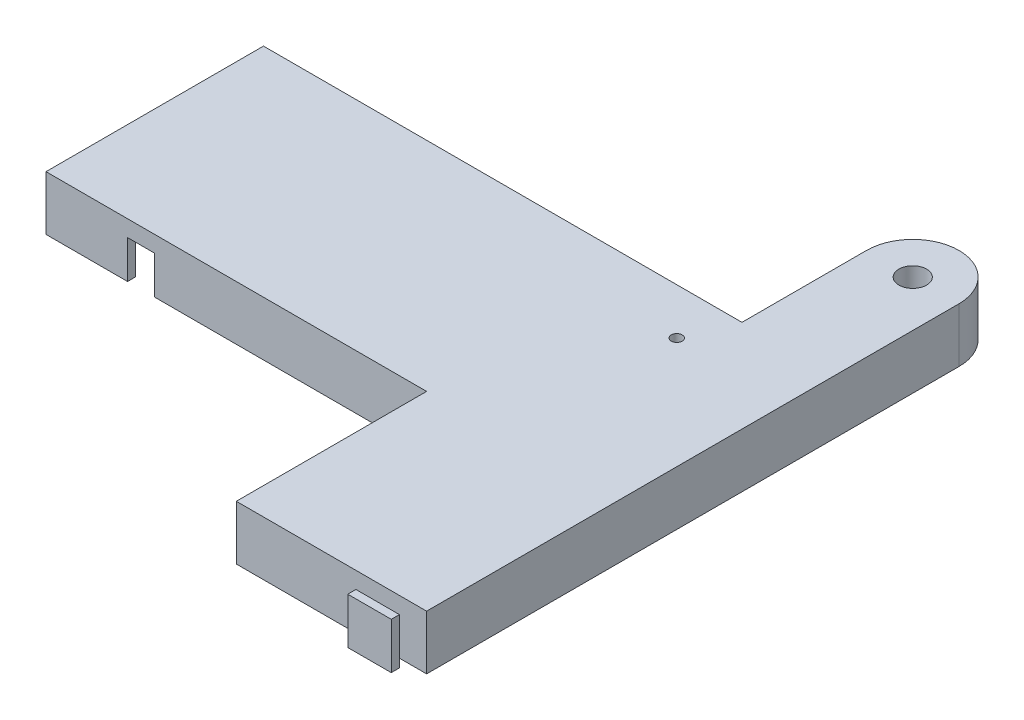
SolidWorks part; units mm, degrees
ref_plane "Front Plane" through (0, 0, 0) normal (0, 0, 1) x (1, 0, 0)
ref_plane "Top Plane" through (0, 0, 0) normal (0, 1, 0) x (1, 0, 0)
ref_plane "Right Plane" through (0, 0, 0) normal (1, 0, 0) x (0, 0, -1)
sketch "CornerSketch1" plane through (0, 0, 0) normal (0, 1, 0) x (1, 0, 0)
  line L0 (210, -70) -> (140, -70)
  line L2 (0, 80) -> (176, 80)
  line L5 (140, -70) -> (140, 0)
  line L6 (140, 0) -> (0, 0)
  line L7 (0, 80) -> (0, 0)
  line L8 (176, 125.825) -> (176, 80)
  line L10 (210, 125.825) -> (210, -70)
  arc A0 (210, 125.825) -> (176, 125.825) centre (193, 125.825) ccw
  dimension "D3" = 34
  dimension "D4" = 70
  dimension "D6" = 45.825
  dimension "D2" = 210
  dimension "D5" = 150
  dimension "D7" = 80
extrude "CornerBoss-Extrude1" add sketch "CornerSketch1" along normal blind 20
shell "Shell1" thickness 3 removed face at (131.5, 0, -36.0813)
sketch "PadSketch2" plane through (0, 17, 0) normal (0, -1, 0) x (1, 0, 0)
  line L0 (210, 70) -> (210, -125.825) construction
  line L1 (176, -80) -> (0, -80) construction
  circle A0 centre (193, -125.825) radius 12
  circle A1 centre (169, -63) radius 5
  dimension "D2" = 10
  dimension "D1" = 24
  dimension "D3" = 41
  dimension "D4" = 17
extrude "PadBoss-Extrude2" add sketch "PadSketch2" along normal blind 10
sketch "StepperRodHoleSketch3" plane through (0, 7, 0) normal (0, -1, 0) x (1, 0, 0)
  circle A0 centre (193, -125.825) radius 5.1
  circle A1 centre (169, -63) radius 2
  dimension "D1" = 10.2
  dimension "D2" = 4
extrude "StepperRodHoleCut-Extrude1" cut sketch "StepperRodHoleSketch3" against normal through all
sketch "ThreadedNutMountHolesSketch4" plane through (0, 7, 0) normal (0, -1, 0) x (-1, 0, 0)
  circle A8 centre (-193, 133.825) radius 2
  circle A9 centre (-185, 125.825) radius 2
  circle A10 centre (-201, 125.825) radius 2
  circle A11 centre (-193, 117.825) radius 2
  dimension "D1" = 4
  dimension "D3" = 16
  dimension "D4" = 8
  dimension "D5" = 16
extrude "ThreadedNutMountHolesCut-Extrude2" cut sketch "ThreadedNutMountHolesSketch4" against normal blind 10
sketch "TLPegHoleSketch1" plane through (0, 0, 0) normal (-1, 0, 0) x (0, 0, 1)
  line L1 (-70, 14) -> (-60, 14)
  line L2 (-70, 14) -> (-70, 0)
  line L3 (-70, 0) -> (-60, 0)
  line L4 (-60, 14) -> (-60, 0)
  line L7 (-80, 0) -> (0, 0) construction
  line L8 (-80, 20) -> (-80, 0) construction
  dimension "D2" = 10
  dimension "D1" = 10
  dimension "D3" = 14
extrude "TLPegHoleCut-Extrude1" cut sketch "TLPegHoleSketch1" against normal blind 3
sketch "BottomPegSketch2" plane through (0, 0, 70) normal (0, 0, 1) x (1, 0, 0)
  line L1 (190.1, 13.9) -> (199.9, 13.9)
  line L2 (190.1, 13.9) -> (190.1, 0)
  line L3 (190.1, 0) -> (199.9, 0)
  line L4 (199.9, 13.9) -> (199.9, 0)
  line L6 (210, 20) -> (210, 0) construction
  line L7 (140, 0) -> (210, 0) construction
  dimension "D2" = 13.9
  dimension "D3" = 9.8
  dimension "D1" = 10.1
extrude "BottomPegBoss-Extrude1" add sketch "BottomPegSketch2" along normal blind 3.1
sketch "BottomPegCapSketch3" plane through (0, 0, 73.1) normal (0, 0, 1) x (1, 0, 0)
  line L1 (187.1, 17) -> (203.1, 17)
  line L2 (187.1, 17) -> (187.1, 0)
  line L3 (187.1, 0) -> (203.1, 0)
  line L4 (203.1, 17) -> (203.1, 0)
  line L6 (140, 0) -> (190.1, 0) construction
  line L7 (190.1, 13.9) -> (190.1, 0) construction
  dimension "D1" = 16
  dimension "D3" = 17
  dimension "D2" = 3
extrude "BottomPegCapBoss-Extrude2" add sketch "BottomPegCapSketch3" along normal blind 3
sketch "BedCenterHoleCutSketch1" plane through (0, 0, 0) normal (0, 0, 1) x (1, 0, 0)
  line L0 (0, 0) -> (140, 0) construction
  line L1 (30, 14) -> (40, 14)
  line L2 (30, 14) -> (30, 0)
  line L3 (30, 0) -> (40, 0)
  line L4 (40, 14) -> (40, 0)
  line L5 (140, 20) -> (140, 0) construction
  dimension "D2" = 10
  dimension "D1" = 14
  dimension "D3" = 100
extrude "BedCenterHoleCut-Extrude1" cut sketch "BedCenterHoleCutSketch1" against normal blind 3
equation "\"BedThickness\"= 20mm"
equation "\"BedToBuildPlateStandoffHolesDistanceFromLeftOrRight\"= \"BuildPlateStandoffHolesDistanceFromLeftOrRight\" + \"BedIncreasedByWidth\" / 2'Equals 17"
equation "\"BedToBuildPlateStandoffHolesDistanceFromBack\"= \"BuildPlateStandoffHolesDistanceFromBack\" + \"BedIncreasedByLength\" / 2'Equals 41"
equation "\"BedLLongSide\"= \"BedThirdSize\" * 3'Equals 210"
equation "\"BedLShortSide\"= \"BedThirdSize\" * 2'Equals 140"
equation "\"BedIncreasedByWidth\"= 20mm"
equation "\"BedIncreasedByLength\"= 0mm"
equation "\"BedThirdSize\"= 70mm"
equation "\"BedOverlap\"= 20mm"
equation "\"D3@TLPegHoleSketch1\"=\"BedPegHoleHeight\""
equation "\"StandardWallThickness\"= 3mm"
equation "\"D1@CornerBoss-Extrude1\"=\"BedThickness\""
equation "\"D1@TLPegHoleCut-Extrude1\" = \"StandardWallThickness\""
equation "\"D1@BottomPegBoss-Extrude1\"=\"BedPegBoss\""
equation "\"D2@BottomPegCapSketch3\"=\"StandardWallThickness\""
equation "\"D1@BottomPegCapBoss-Extrude2\" = \"StandardWallThickness\""
equation "\"LeadScrewNutPadSize\"= \"LeadScrewNutMountingHoleFlangeDiameter\" + 2mm'Equals 24"
equation "\"BedToBuildPlateStandoffPadSize\"= 10mm"
equation "\"D1@PadSketch2\" = \"LeadScrewNutPadSize\""
equation "\"D2@PadSketch2\" = \"BedToBuildPlateStandoffPadSize\""
equation "\"D3@PadSketch2\"=\"BedToBuildPlateStandoffHolesDistanceFromBack\""
equation "\"D4@PadSketch2\"=\"BedToBuildPlateStandoffHolesDistanceFromLeftOrRight\""
equation "\"D2@StepperRodHoleSketch3\"=\"M3HeatInsertHoleDiameter\""
equation "\"BuildPlateStandoffHolesDistanceFromLeftOrRight\"= 7mm"
equation "\"BuildPlateStandoffHolesDistanceFromBack\"= 41mm"
equation "\"D1@StepperRodHoleSketch3\"=\"LeadScrewNutInnerShaftFlangeDiameter\""
equation "\"BedLWidth\"= \"BedThirdSize\"'Equals 70"
equation "\"D4@CornerSketch1\"=\"BedLWidth\" + \"BedIncreasedByLength\"/2"
equation "\"D2@CornerSketch1\"=\"BedLLongSide\""
equation "\"D7@CornerSketch1\"=\"BedLWidth\" +\"BedOverlap\"/2"
equation "\"DistanceFromBedSideToStepperHole\"= ( \"DistanceBetweenLeftToRightStepperHoles\" - \"BedWidth\" ) / 2'Equals 45.825"
equation "\"RailThickness\"= .125in'Spec"
equation "\"DistanceBetweenLeftToRightStepperHoles\"= \"FrontBackRailLength\" - \"StepperMountingHoleOffsetFromLeftOrRightSide\" * 2 - \"StepperMountingHoleDistance\"'Equals 461.65"
equation "\"BedInnerSquareWidth\"= \"BedThirdSize\" * 3'Equals 210"
equation "\"FrontBackRailLength\"= 510mm"
equation "\"StepperMountingHoleOffsetFromItsSide\"= 5.5mm'Spec"
equation "\"StepperMountingHoleOffsetFromLeftOrRightSide\"= \"StepperMountingHoleOffsetFromItsSide\" + \"RailThickness\""
equation "\"StepperMountingHoleDistance\"= 31mm'Spec"
equation "\"BedWidth\"= \"BedInnerSquareWidth\" + \"BedLWidth\" * 2 + \"BedIncreasedByWidth\"'Equals 370"
equation "\"D6@CornerSketch1\"=\"DistanceFromBedSideToStepperHole\""
equation "\"DistanceFromBedFrontToStepperHole\"= \"LeadScrewNutPadSize\" + 10mm"
equation "\"D3@CornerSketch1\"=\"DistanceFromBedFrontToStepperHole\""
equation "\"D5@CornerSketch1\"=\"BedLShortSide\" +\"BedIncreasedByWidth\"/2"
equation "\"LeadScrewNutInnerShaftFlangeDiameter\"= 10.2mm'Spec"
equation "\"LeadScrewNutMountHoleDiameter\" = \"M3HeatInsertHoleDiameter\"'Spec is 4.1 but smaller for tapping"
equation "\"LeadScrewNutMountingHoleFlangeDiameter\"= 22mm'Spec"
equation "\"LeadScrewNutMountingHoleDistance\"= 16mm'Spec"
equation "\"D3@ThreadedNutMountHolesSketch4\"=\"LeadScrewNutMountingHoleDistance\""
equation "\"D4@ThreadedNutMountHolesSketch4\"=\"LeadScrewNutMountingHoleDistance\"/2"
equation "\"D5@ThreadedNutMountHolesSketch4\"=\"LeadScrewNutMountingHoleDistance\""
equation "\"D2@ThreadedNutMountHolesSketch4\"=\"LeadScrewNutMountingHoleDistance\"/2"
equation "\"D1@ThreadedNutMountHolesSketch4\"=\"LeadScrewNutMountHoleDiameter\""
equation "\"LeadScrewNutPadDepth\"= \"BedThickness\" / 2'Equals 10"
equation "\"D1@ThreadedNutMountHolesCut-Extrude2\"=\"LeadScrewNutPadDepth\""
equation "\"D1@PadBoss-Extrude2\"= \"LeadScrewNutPadDepth\""
equation "\"BedPegHoleWidth\"= 10mm"
equation "\"BedPegHoleHeight\"= \"BedThickness\" - \"StandardWallThickness\" * 2'Equals 14"
equation "\"BedPegWidth\"= \"BedPegHoleWidth\" - .1mm * 2'For easier assembly"
equation "\"BedPegHeight\"= \"BedPegHoleHeight\" - .1mm'For easier assembly"
equation "\"BedTopPegOffsetFromSide\"= 10mm"
equation "\"BedPegBoss\"= \"StandardWallThickness\" + .1mm'For easier assembly"
equation "\"BedPegCapHeight\"= \"BedThickness\" - \"StandardWallThickness\"'Equals 17"
equation "\"BedPegCapWidth\"= \"BedThickness\" / 2 + \"StandardWallThickness\" * 2'Equals 16"
equation "\"D1@TLPegHoleSketch1\"=\"BedTopPegOffsetFromSide\""
equation "\"D2@TLPegHoleSketch1\"=\"BedPegHoleWidth\""
equation "\"D3@BottomPegSketch2\"=\"BedPegWidth\""
equation "\"D2@BottomPegSketch2\"=\"BedPegHeight\""
equation "\"D1@BottomPegCapSketch3\"=\"BedPegCapWidth\""
equation "\"D3@BottomPegCapSketch3\"=\"BedPegCapHeight\""
equation "\"D1@BedCenterHoleCutSketch1\" = \"BedPegHoleHeight\""
equation "\"D2@BedCenterHoleCutSketch1\" = \"BedPegHoleWidth\""
equation "\"D3@BedCenterHoleCutSketch1\" = \"BedInnerSquareWidth\" / 2 - \"BedPegHoleWidth\" / 2"
equation "\"D1@BedCenterHoleCut-Extrude1\"=\"StandardWallThickness\""
equation "\"M3HeatInsertHoleDiameter\"= 4mm'Spec"
